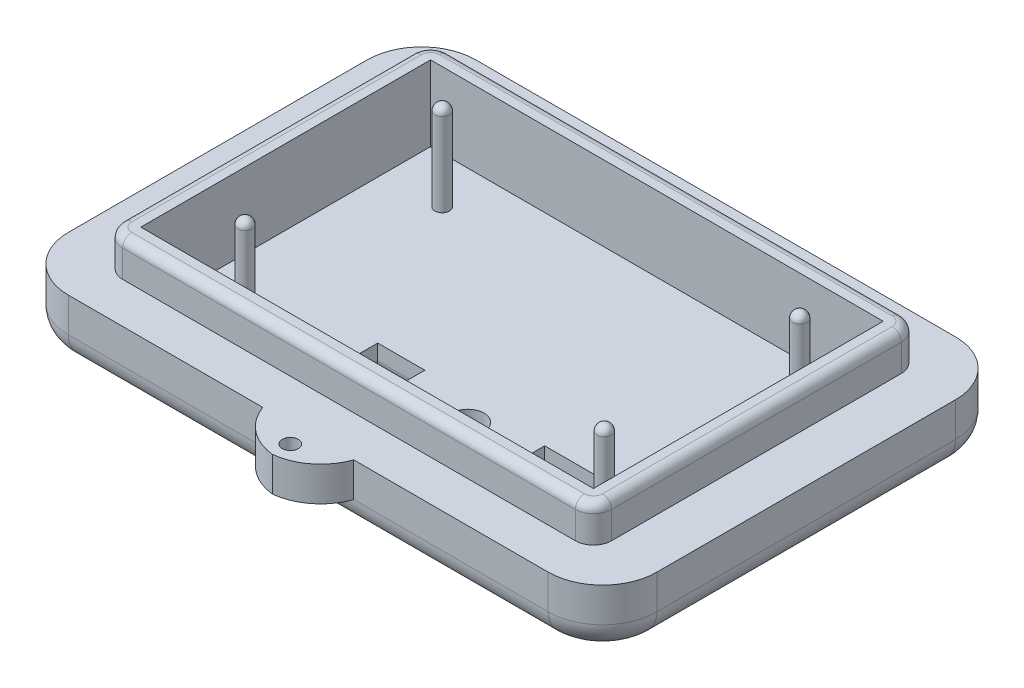
SolidWorks part; units mm, degrees
ref_plane "Front Plane" through (0, 0, 0) normal (0, 0, 1) x (1, 0, 0)
ref_plane "Top Plane" through (0, 0, 0) normal (0, 1, 0) x (1, 0, 0)
ref_plane "Right Plane" through (0, 0, 0) normal (1, 0, 0) x (0, 0, -1)
sketch "Sketch1" plane through (0, 0, 0) normal (0, 1, 0) x (1, 0, 0)
  line L1 (0, 0) -> (82.55, 0)
  line L2 (0, 0) -> (0, 57.15)
  line L3 (0, 57.15) -> (82.55, 57.15)
  line L4 (82.55, 0) -> (82.55, 57.15)
  dimension "D1" = 57.15
  dimension "D2" = 82.55
extrude "Boss-Extrude1" add sketch "Sketch1" along normal blind 8.636
fillet "Fillet2" radius 7.62 4 edges at (82.55, 4.318, -57.15) (82.55, 4.318, 0) (0, 4.318, 0) (0, 4.318, -57.15)
fillet "Fillet3" radius 3.81 8 edges at (80.3182, 0, -54.9182) (82.55, 0, -28.575) (80.3182, 0, -2.2318) (41.275, 0, 0) (2.2318, 0, -2.2318) (0, 0, -28.575) (2.2318, 0, -54.9182) (41.275, 0, -57.15)
sketch "Sketch2" plane through (0, 8.636, 0) normal (0, 1, 0) x (1, 0, 0)
  line L0 (0, 28.575) -> (82.55, 28.575) construction
  line L1 (0, 49.53) -> (0, 7.62) construction
  line L2 (82.55, 7.62) -> (82.55, 49.53) construction
  line L4 (9.525, 8.255) -> (73.025, 8.255)
  line L5 (9.525, 8.255) -> (9.525, 48.895)
  line L6 (9.525, 48.895) -> (73.025, 48.895)
  line L7 (73.025, 8.255) -> (73.025, 48.895)
  line L8 (9.525, 8.255) -> (73.025, 48.895) construction
  line L9 (9.525, 48.895) -> (73.025, 8.255) construction
  point P6 (41.275, 28.575)
  dimension "D1" = 40.64
  dimension "D2" = 63.5
extrude "Cut-Extrude1" cut sketch "Sketch2" against normal blind 5.461
sketch "Sketch7" plane through (0, 8.636, 0) normal (0, 1, 0) x (1, 0, 0)
  line L14 (6.985, 51.435) -> (6.985, 5.715)
  line L15 (6.985, 5.715) -> (75.565, 5.715)
  line L16 (75.565, 5.715) -> (75.565, 51.435)
  line L17 (75.565, 51.435) -> (6.985, 51.435)
  line L18 (6.985, 51.435) -> (6.985, 5.715)
  line L19 (6.985, 5.715) -> (75.565, 5.715)
  line L20 (75.565, 5.715) -> (75.565, 51.435)
  line L21 (75.565, 51.435) -> (6.985, 51.435)
  dimension "D1" = 2.54
extrude "Boss-Extrude3" add sketch "Sketch7" along normal blind 5.08
sketch "Sketch8" plane through (0, 13.716, 0) normal (0, 1, 0) x (1, 0, 0)
  line L8 (73.025, 48.895) -> (9.525, 48.895)
  line L9 (9.525, 48.895) -> (9.525, 8.255)
  line L10 (9.525, 8.255) -> (73.025, 8.255)
  line L11 (73.025, 8.255) -> (73.025, 48.895)
  line L12 (73.025, 48.895) -> (9.525, 48.895)
  line L13 (9.525, 48.895) -> (9.525, 8.255)
  line L14 (9.525, 8.255) -> (73.025, 8.255)
  line L15 (73.025, 8.255) -> (73.025, 48.895)
  dimension "D1" = 2.54
extrude "Cut-Extrude3" cut sketch "Sketch8" against normal blind 5.08
sketch "Sketch5" plane through (0, 3.175, 0) normal (0, 1, 0) x (1, 0, 0)
  line L3 (9.525, 8.255) -> (73.025, 8.255) construction
  line L4 (73.025, 8.255) -> (73.025, 48.895) construction
  circle A0 centre (17.665, 42.392) radius 1.016
  circle A1 centre (17.665, 14.732) radius 1.016
  circle A2 centre (67.945, 42.259) radius 1.016
  circle A3 centre (67.945, 14.859) radius 1.016
  dimension "D5" = 2.032
  dimension "D6" = 2.032
  dimension "D7" = 2.032
  dimension "D8" = 2.032
  dimension "D11" = 6.604
  dimension "D2" = 27.66
  dimension "D3" = 6.477
  dimension "D4" = 50.28
  dimension "D9" = 27.4
  dimension "D10" = 5.08
  dimension "D12" = 5.08
  dimension "D13" = 50.28
extrude "Boss-Extrude4" add sketch "Sketch5" along normal blind 12.7
sketch "Sketch4" plane through (0, 3.175, 0) normal (0, 1, 0) x (1, 0, 0)
  line L4 (66.471, 20.559) -> (53.871, 20.559)
  line L5 (66.471, 20.559) -> (66.471, 15.559)
  line L6 (66.471, 15.559) -> (53.871, 15.559)
  line L7 (53.871, 20.559) -> (53.871, 15.559)
  line L8 (66.471, 20.559) -> (53.871, 15.559) construction
  line L9 (66.471, 15.559) -> (53.871, 20.559) construction
  line L11 (36.285, 21.336) -> (29.681, 21.336)
  line L12 (36.285, 21.336) -> (36.285, 14.732)
  line L13 (36.285, 14.732) -> (29.681, 14.732)
  line L14 (29.681, 21.336) -> (29.681, 14.732)
  line L15 (36.285, 21.336) -> (29.681, 14.732) construction
  line L16 (36.285, 14.732) -> (29.681, 21.336) construction
  circle A0 centre (45.641, 18.034) radius 2.25
  circle A1 centre (17.665, 14.732) radius 1.016 construction
  circle A2 centre (67.945, 14.859) radius 1.016 construction
  point P7 (60.171, 18.059)
  point P15 (32.983, 18.034)
  dimension "D3" = 4.5
  dimension "D4" = 5.7
  dimension "D2" = 15.96
  dimension "D5" = 12.6
  dimension "D6" = 5
  dimension "D7" = 20.83
  dimension "D8" = 6.604
  dimension "D9" = 6.604
  dimension "D10" = 0
  dimension "D11" = 18.62
  dimension "D13" = 0
extrude "Cut-Extrude2" cut sketch "Sketch4" against normal blind 7.366
fillet "Fillet7" radius 1.016 3 edges at (17.665, 15.875, -13.716) (17.665, 15.875, -41.376) (67.945, 15.875, -41.243)
fillet "Fillet8" radius 2.54 4 edges at (75.565, 11.176, -51.435) (75.565, 11.176, -5.715) (6.985, 11.176, -5.715) (6.985, 11.176, -51.435)
sketch "Sketch9" plane through (0, 0, 0) normal (0, 0, 1) x (1, 0, 0)
  line L0 (41.275, 8.636) -> (41.275, 3.81) construction
  line L1 (7.62, 8.636) -> (74.93, 8.636) construction
  line L2 (7.62, 3.81) -> (74.93, 3.81) construction
  line L4 (47.6519, 8.636) -> (34.8981, 8.636)
  line L5 (47.6519, 8.636) -> (47.6519, 3.81)
  line L6 (47.6519, 3.81) -> (34.8981, 3.81)
  line L7 (34.8981, 8.636) -> (34.8981, 3.81)
  line L8 (47.6519, 8.636) -> (34.8981, 3.81) construction
  line L9 (47.6519, 3.81) -> (34.8981, 8.636) construction
  point P6 (41.275, 6.223)
extrude "Boss-Extrude5" add sketch "Sketch9" along normal blind 5.08
fillet "Fillet10" radius 7.62 2 edges at (47.6519, 6.223, 5.08) (34.8981, 6.223, 5.08)
fillet "Fillet11" radius 1.27 8 edges at (74.8211, 13.716, -50.6911) (75.565, 13.716, -28.575) (74.8211, 13.716, -6.4589) (41.275, 13.716, -5.715) (7.7289, 13.716, -6.4589) (7.7289, 13.716, -50.6911) (6.985, 13.716, -28.575) (41.275, 13.716, -51.435)
fillet "Fillet12" radius 1.016 1 edges at (67.945, 15.875, -13.843)
sketch "Sketch17" plane through (0, 3.81, 0) normal (0, -1, 0) x (1, 0, 0)
  line L0 (41.275, 5.0371) -> (41.275, 0) construction
  point P3 (41.275, 2.5186)
hole_wizard "#4-40 Tapped Hole2" positions "Sketch18" profile "Sketch19" tap size "#4-40" standard "ANSI Inch"
sketch "Sketch18" plane through (0, 3.81, 0) normal (0, -1, 0) x (-1, 0, 0)
  point P0 (-41.275, -2.5186)
sketch "Sketch19" plane through (41.275, 3.81, 2.5186) normal (1, 0, 0) x (0, 0, -1)
  line L0 (0, 0) -> (0, 8.2992)
  line L1 (0, 8.2992) -> (1.1303, 7.62)
  line L2 (1.1303, 7.62) -> (1.1303, 0.7779)
  line L3 (1.1303, 0.7779) -> (2.0574, 0)
  line L5 (2.0574, 0) -> (0, 0)
  line L6 (-1.1303, 0.7779) -> (-2.0574, 0) construction
  line L10 (0, 8.2992) -> (-1.1303, 7.62) construction
  line L11 (0, -6.35) -> (0, 107.95) construction
  dimension "Tap Drill Dia." = 2.2606
  dimension "Tap Drill Depth" = 7.62
  dimension "Near C'Sink Dia." = 4.1148
  dimension "Near C'Sink Angle" = 100
  dimension "Drill Angle" = 118
cosmetic thread "Hole Thread2" parameters "D1"=4.826, "D2"=2.8448
fillet "Fillet13" radius 1.016 9 edges at (66.471, 0, -18.059) (60.171, 0, -15.559) (53.871, 0, -18.059) (60.171, 0, -20.559) (45.641, 0, -20.284) (29.681, 0, -18.034) (32.983, 0, -14.732) (36.285, 0, -18.034) (32.983, 0, -21.336)
